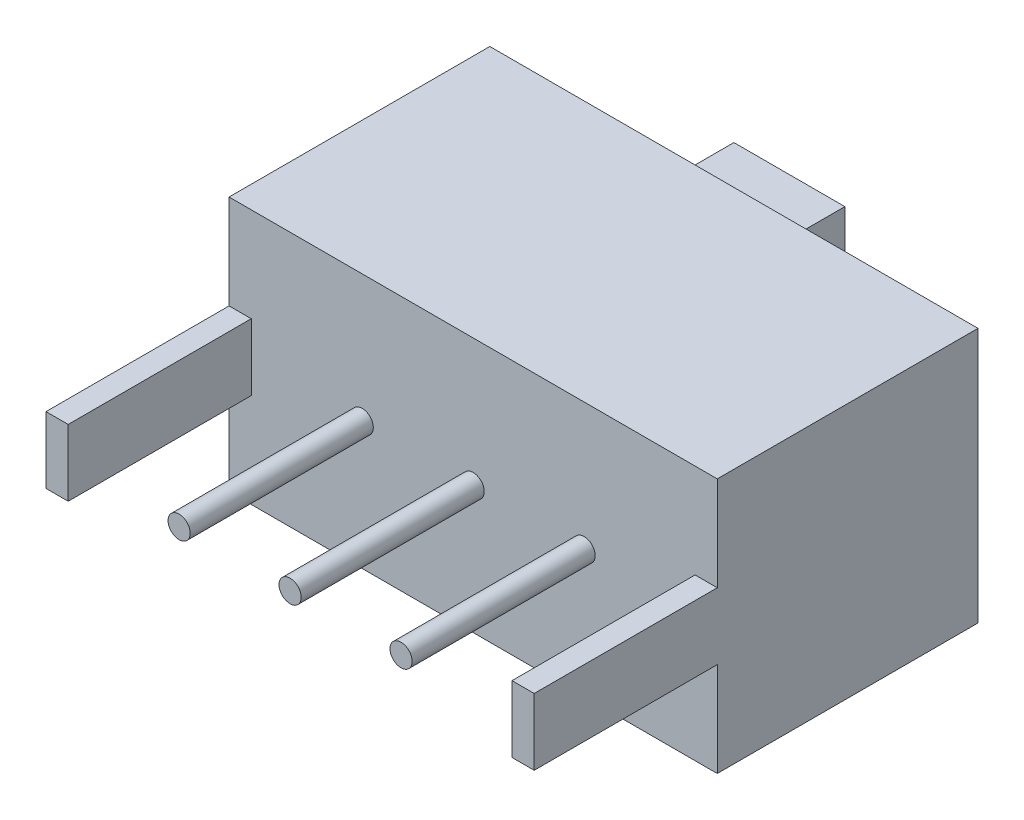
SolidWorks part; units mm, degrees
ref_plane "前视基准面" through (0, 0, 0) normal (0, 0, 1) x (1, 0, 0)
ref_plane "上视基准面" through (0, 0, 0) normal (0, 1, 0) x (1, 0, 0)
ref_plane "右视基准面" through (0, 0, 0) normal (1, 0, 0) x (0, 0, -1)
other "Configuration Table"
sketch "草图1" plane through (0, 0, 0) normal (0, 0, 1) x (1, 0, 0)
  line L1 (0, 0) -> (8.8, 0)
  line L2 (0, 0) -> (0, -4.6)
  line L3 (0, -4.6) -> (8.8, -4.6)
  line L4 (8.8, 0) -> (8.8, -4.6)
  line L5 (2.3, -1.2) -> (6.5, -1.2)
  line L6 (2.3, -1.2) -> (2.3, -3.4)
  line L7 (2.3, -3.4) -> (6.5, -3.4)
  line L8 (6.5, -1.2) -> (6.5, -3.4)
  line L9 (2.4, -1.3) -> (4.4, -1.3)
  line L10 (2.4, -1.3) -> (2.4, -3.3)
  line L11 (2.4, -3.3) -> (4.4, -3.3)
  line L12 (4.4, -1.3) -> (4.4, -3.3)
  point P13 (4.4, -4.6)
  point P14 (2.3, -2.3)
  point P15 (2.4, -2.3)
  point P16 (0, -2.3)
  point P17 (4.4, -1.2)
  dimension "D1" = 8.8
  dimension "D2" = 4.6
  dimension "D3" = 4.2
  dimension "D4" = 2.2
  dimension "D5" = 2
  dimension "D7" = 2
extrude "凸台-拉伸1" add sketch "草图1" along normal blind 4.7 contours L2 L3 L4 L1
extrude "切除-拉伸1" cut sketch "草图1<3>" along normal blind 0.2 contours L5 L8 L7 L6 | L12 L11 L10 L9
sketch "草图1<3>" plane through (0, 0, 0) normal (0, 0, 1) x (1, 0, 0) same geometry as "草图1"
extrude "凸台-拉伸2" add sketch "草图1<4>" against normal blind 2 contours L12 L11 L10 L9
sketch "草图1<4>" plane through (0, 0, 0) normal (0, 0, 1) x (1, 0, 0) same geometry as "草图1"
sketch "草图2" plane through (0, 0, 4.7) normal (0, 0, 1) x (1, 0, 0)
  line L5 (8.8, 0) -> (8.8, -4.6) construction
  line L6 (8.8, -1.7) -> (8.4, -1.7)
  line L7 (8.8, -1.7) -> (8.8, -2.9)
  line L8 (8.8, -2.9) -> (8.4, -2.9)
  line L9 (8.4, -1.7) -> (8.4, -2.9)
  line L11 (0, -1.7) -> (0.4, -1.7)
  line L12 (0, -1.7) -> (0, -2.9)
  line L13 (0, -2.9) -> (0.4, -2.9)
  line L14 (0.4, -1.7) -> (0.4, -2.9)
  line L15 (0, 0) -> (8.8, -4.6)
  line L17 (0, 0) -> (0, -4.6) construction
  circle A0 centre (2.4, -2.3) radius 0.2
  circle A1 centre (4.4, -2.3) radius 0.2
  circle A2 centre (6.4, -2.3) radius 0.2
  point P4 (0, -2.3)
  point P5 (8.4, -2.3)
  dimension "D3" = 0.4
  dimension "D4" = 0.4
  dimension "D1" = 2
  dimension "D2" = 2
  dimension "D5" = 1.2
extrude "凸台-拉伸3" add sketch "草图2" along normal blind 3.3 contours L13 L14 L11 L12 | A0 | A1 | A2 | L8 L9 L6 L7
